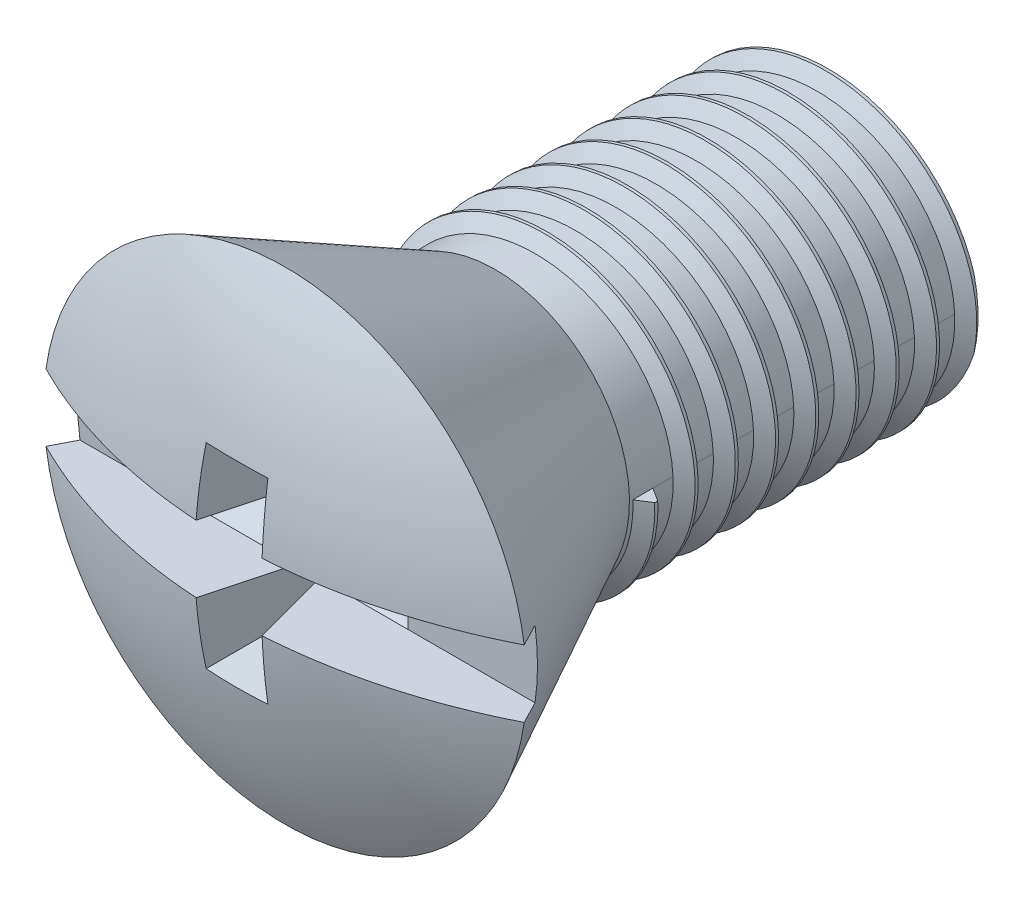
SolidWorks part; units mm, degrees
material "Stainless Steel (ferritic)"
ref_plane "Front" through (0, 0, 0) normal (0, 0, 1) x (1, 0, 0)
ref_plane "Top" through (0, 0, 0) normal (0, 1, 0) x (1, 0, 0)
ref_plane "Right" through (0, 0, 0) normal (1, 0, 0) x (0, 0, -1)
sketch "Sketch2" plane through (0, 0, 0) normal (0, 0, 1) x (1, 0, 0)
  circle A0 centre (0, 0) radius 4.572
  dimension "D1" = 9.144
extrude "Boss-Extrude1" add sketch "Sketch2" along normal blind 5.08
sketch "Sketch3" plane through (0, 0, 0) normal (1, 0, 0) x (0, 0, -1)
  line L0 (0, 0) -> (4.7808, 0) construction
  line L1 (0, -4.572) -> (0, 4.572) construction
  line L2 (0, 2.54) -> (-3.9805, 4.572)
  line L3 (0, 4.572) -> (-5.08, 4.572) construction
  line L4 (-5.08, 4.572) -> (-5.08, -4.572) construction
  line L5 (0, 2.54) -> (0, 4.826)
  line L6 (0, 4.826) -> (-5.334, 4.826)
  line L7 (-5.334, 4.826) -> (-5.334, 0)
  line L8 (-5.334, 0) -> (-5.08, 0)
  line L9 (0, -2.54) -> (-1.4251, -4.572) construction
  line L11 (-5.08, -4.572) -> (0, -4.572) construction
  arc A0 (-3.9805, 4.572) -> (-5.08, 0) centre (4.9756, 0) ccw
  dimension "D1" = 82
  dimension "D2" = 5.08
  dimension "D3" = 5.08
  dimension "D4" = 0.254
  dimension "D5" = 0.254
revolve "Cut-Revolve1" cut sketch "Sketch3" angle 360 about L0
sketch "Sketch4" plane through (0, 0, 0) normal (0, 0, -1) x (-1, 0, 0)
  circle A0 centre (0, 0) radius 2.54
extrude "Boss-Extrude2" add sketch "Sketch4" along normal blind 6.35
sketch "Sketch5" plane through (0, 0, -6.35) normal (0, 0, -1) x (-1, 0, 0)
  circle A0 centre (0, 0) radius 2.54 construction
  circle A1 centre (0, 0) radius 2.54
curve "Helix/Spiral1" pitch 0.762 height 6.096 turns 8
sketch "Sketch6" plane through (0, 0, 0) normal (0, -1, 0) x (0, 0, -1)
  line L8 (0.8255, -2.54) -> (0.4445, -2.54)
  line L9 (0.4445, -2.54) -> (0.6063, -2.794)
  line L10 (0.6063, -2.794) -> (0.6637, -2.794)
  line L11 (0.6637, -2.794) -> (0.8255, -2.54)
  line L12 (0, -2.54) -> (6.35, -2.54) construction
  point P0 (0.635, -2.54)
  point P5 (0.8255, -2.54)
  point P8 (0.8255, -2.54)
  point P9 (0.6873, -2.794)
  point P10 (0.6112, -2.794)
  dimension "D1" = 0.381
  dimension "D2" = 65
  dimension "D3" = 0.254
sweep "Sweep1" add profiles "Sketch6" path "Helix/Spiral1"
ref_plane "Plane1" through (0, 0, 5.08) normal (0, 0, 1) x (1, 0, 0)
sketch "Sketch7" plane through (0, 0, 5.08) normal (0, 0, 1) x (1, 0, 0)
  line L1 (4.572, -0.635) -> (-4.572, -0.635)
  line L2 (4.572, -0.635) -> (4.572, 0.635)
  line L3 (4.572, 0.635) -> (-4.572, 0.635)
  line L4 (-4.572, -0.635) -> (-4.572, 0.635)
  line L5 (4.572, -0.635) -> (-4.572, 0.635) construction
  line L6 (4.572, 0.635) -> (-4.572, -0.635) construction
  circle A1 centre (0, 0) radius 4.572 construction
  point P0 (0, 0)
  point P6 (-4.572, 0)
  dimension "D1" = 1.27
extrude "Cut-Extrude1" cut sketch "Sketch7" against normal blind 1.524
sketch "Sketch8" plane through (0, 0, 5.08) normal (0, 0, 1) x (1, 0, 0)
  line L1 (-0.635, -1.905) -> (0.635, -1.905)
  line L2 (-0.635, -1.905) -> (-0.635, 1.905)
  line L3 (-0.635, 1.905) -> (0.635, 1.905)
  line L4 (0.635, -1.905) -> (0.635, 1.905)
  line L5 (-0.635, -1.905) -> (0.635, 1.905) construction
  line L6 (-0.635, 1.905) -> (0.635, -1.905) construction
  point P0 (0, 0)
  point P6 (0, 0)
  dimension "D1" = 3.81
  dimension "D2" = 1.27
extrude "Cut-Extrude2" cut sketch "Sketch8" against normal blind 2.794 draft 15 contours L2 L1 L4 L3
sketch "Sketch9" plane through (0, 0, 3.556) normal (0, 0, 1) x (1, 0, 0)
  line L0 (-1.905, -0.635) -> (1.905, -0.635)
  line L1 (-1.905, -0.635) -> (-1.905, 0.635)
  line L2 (-1.905, 0.635) -> (1.905, 0.635)
  line L3 (1.905, -0.635) -> (1.905, 0.635)
  point P4 (0, -0.635)
  point P7 (1.905, 0)
  dimension "D1" = 1.27
  dimension "D2" = 3.81
extrude "Cut-Extrude3" cut sketch "Sketch9" against normal blind 2.54 draft 20
